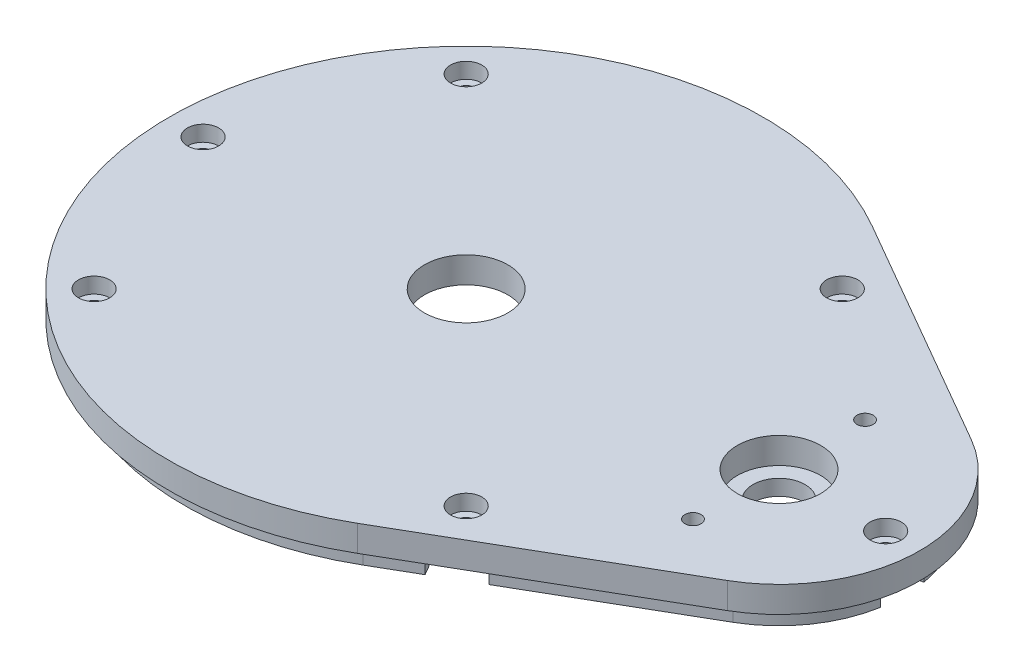
SolidWorks part; units mm, degrees
ref_plane "Front Plane" through (0, 0, 0) normal (0, 0, 1) x (1, 0, 0)
ref_plane "Top Plane" through (0, 0, 0) normal (0, 1, 0) x (1, 0, 0)
ref_plane "Right Plane" through (0, 0, 0) normal (1, 0, 0) x (0, 0, -1)
sketch "Sketch1" plane through (0, 0, 0) normal (0, 1, 0) x (1, 0, 0)
  line L8 (45, -16.5) -> (45, 16.5) construction
  line L9 (13.5, -49.3634) -> (58.5, -23.3827)
  line L10 (13.5, 49.3634) -> (58.5, 23.3827)
  circle A0 centre (-15, 0) radius 46.5 construction
  circle A1 centre (45, 0) radius 16.5 construction
  circle A2 centre (-15, 0) radius 8
  circle A3 centre (45, 0) radius 8
  circle A4 centre (45, 16.5) radius 1.55
  circle A5 centre (45, -16.5) radius 1.55
  circle A8 centre (-15, 0) radius 57 construction
  circle A9 centre (45, 0) radius 27 construction
  arc A12 (13.5, 49.3634) -> (13.5, -49.3634) centre (-15, 0) ccw
  arc A13 (58.5, 23.3827) -> (58.5, -23.3827) centre (45, 0) cw
  point P0 (0, 0)
  point P17 (45, 0)
  point P18 (45, 0)
extrude "Boss-Extrude1" add sketch "Sketch1" along normal blind 5
sketch "Sketch2" plane through (0, 0, 0) normal (0, -1, 0) x (1, 0, 0)
  circle A0 centre (45, 0) radius 5
  circle A1 centre (45, 0) radius 12
extrude "Boss-Extrude2" add sketch "Sketch2" along normal blind 3
sketch "Sketch4" plane through (0, 0, 0) normal (0, -1, 0) x (1, 0, 0)
  line L1 (12, -46.7654) -> (19.5342, -42.4155)
  line L3 (11, -45.0333) -> (18.5342, -40.6834)
  line L5 (45, 0) -> (68.6354, 4.1676) construction
  line L6 (45, 0) -> (68.6354, -4.1676) construction
  line L8 (68.6354, -4.1676) -> (66.6658, -3.8203)
  line L9 (66.6658, 3.8203) -> (68.6354, 4.1676)
  line L10 (-15, 0) -> (-68.7945, 4.7064) construction
  line L11 (-15, 0) -> (-68.7945, -4.7064) construction
  line L14 (-15, 0) -> (-49.7105, 41.3664) construction
  line L15 (-15, 0) -> (-56.3664, 34.7105) construction
  line L16 (-15, 0) -> (-49.7105, -41.3664) construction
  line L17 (-15, 0) -> (-56.3664, -34.7105) construction
  line L18 (-49.7105, 41.3664) -> (-48.425, 39.8343)
  line L19 (-54.8343, 33.425) -> (-56.3664, 34.7105)
  line L20 (-66.8021, 4.5321) -> (-68.7945, 4.7064)
  line L21 (-68.7945, -4.7064) -> (-66.8021, -4.5321)
  line L22 (-54.8343, -33.425) -> (-56.3664, -34.7105)
  line L23 (-48.425, -39.8343) -> (-49.7105, -41.3664)
  line L24 (57, 20.7846) -> (27.3285, 37.9155)
  line L25 (11, 45.0333) -> (18.5342, 40.6834)
  line L29 (-15, 0) -> (21.0624, 36.0624) construction
  line L30 (17.1653, 38.3124) -> (24.9596, 33.8124) construction
  line L31 (17.1653, 38.3124) -> (19.5342, 42.4155) construction
  line L33 (24.9596, 33.8124) -> (27.3285, 37.9155) construction
  line L34 (26.3285, 36.1834) -> (56, 19.0526)
  line L35 (19.5342, 42.4155) -> (12, 46.7654)
  line L36 (19.5342, 42.4155) -> (18.5342, 40.6834)
  line L37 (27.3285, 37.9155) -> (26.3285, 36.1834)
  line L38 (-15, 0) -> (21.0624, -36.0624) construction
  line L39 (17.1653, -38.3124) -> (24.9596, -33.8124) construction
  line L40 (17.1653, -38.3124) -> (19.5342, -42.4155) construction
  line L41 (24.9596, -33.8124) -> (27.3285, -37.9155) construction
  line L42 (26.3285, -36.1834) -> (56, -19.0526)
  line L43 (27.3285, -37.9155) -> (57, -20.7846)
  line L44 (18.5342, -40.6834) -> (19.5342, -42.4155)
  line L45 (26.3285, -36.1834) -> (27.3285, -37.9155)
  arc A10 (56, 19.0526) -> (66.6658, 3.8203) centre (45, 0) cw
  arc A11 (66.6658, -3.8203) -> (56, -19.0526) centre (45, 0) cw
  arc A12 (57, 20.7846) -> (68.6354, 4.1676) centre (45, 0) cw
  arc A13 (57, -20.7846) -> (68.6354, -4.1676) centre (45, 0) ccw
  arc A18 (12, 46.7654) -> (-49.7105, 41.3664) centre (-15, 0) ccw
  arc A19 (-68.7945, -4.7064) -> (-56.3664, -34.7105) centre (-15, 0) ccw
  arc A20 (11, 45.0333) -> (-48.425, 39.8343) centre (-15, 0) ccw
  arc A21 (-66.8021, -4.5321) -> (-54.8343, -33.425) centre (-15, 0) ccw
  arc A22 (-54.8343, 33.425) -> (-66.8021, 4.5321) centre (-15, 0) ccw
  arc A23 (-56.3664, 34.7105) -> (-68.7945, 4.7064) centre (-15, 0) ccw
  arc A24 (-48.425, -39.8343) -> (11, -45.0333) centre (-15, 0) ccw
  arc A25 (-49.7105, -41.3664) -> (12, -46.7654) centre (-15, 0) ccw
  point P32 (21.0624, 36.0624)
  point P39 (21.0624, -36.0624)
extrude "Boss-Extrude3" add sketch "Sketch4" along normal blind 4
sketch "Sketch5" plane through (0, 5, 0) normal (0, 1, 0) x (1, 0, 0)
  line L0 (-15, 0) -> (-65.45, 0) construction
  line L1 (45, 0) -> (65.45, 0) construction
  line L2 (-15, 0) -> (-50.6735, -35.6735) construction
  line L3 (-15, 0) -> (21.0624, -36.0624) construction
  line L9 (-15, 0) -> (21.0624, 36.0624) construction
  line L11 (-15, 0) -> (45, 0) construction
  line L12 (-15, 0) -> (-50.6735, 35.6735) construction
  circle A18 centre (-65.45, 0) radius 1.55
  circle A21 centre (65.45, 0) radius 1.55
  circle A29 centre (-50.6735, -35.6735) radius 1.55
  circle A33 centre (21.0624, 36.0624) radius 1.55
  circle A35 centre (21.0624, -36.0624) radius 1.55
  circle A36 centre (-50.6735, 35.6735) radius 1.55
  point P39 (-15, 0)
extrude "Cut-Extrude1" cut sketch "Sketch5" against normal blind 5
sketch "Sketch6" plane through (0, 5, 0) normal (0, 1, 0) x (1, 0, 0)
  circle A0 centre (-50.6735, 35.6735) radius 3
  circle A1 centre (-65.45, 0) radius 3
  circle A2 centre (-50.6735, -35.6735) radius 3
  circle A3 centre (21.0624, -36.0624) radius 3
  circle A4 centre (21.0624, 36.0624) radius 3
  circle A5 centre (65.45, 0) radius 3
extrude "Cut-Extrude2" cut sketch "Sketch6" against normal blind 3
